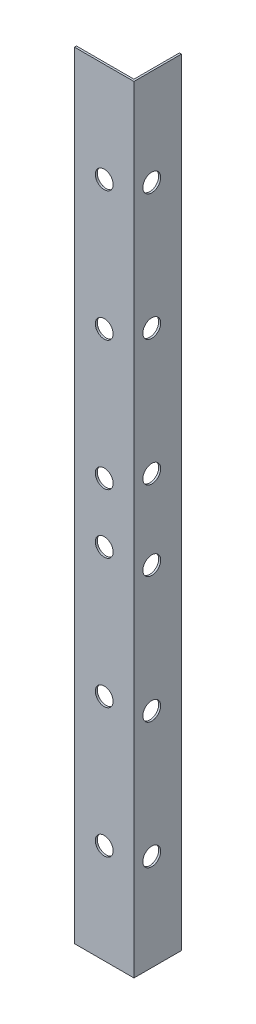
SolidWorks part; units mm, degrees
material "6061-T6 (SS)"
ref_plane "Alzado" through (0, 0, 0) normal (0, 0, 1) x (1, 0, 0)
ref_plane "Planta" through (0, 0, 0) normal (0, 1, 0) x (1, 0, 0)
ref_plane "Vista lateral" through (0, 0, 0) normal (1, 0, 0) x (0, 0, -1)
sketch "Sketch1" plane through (0, 0, 0) normal (0, 1, 0) x (1, 0, 0)
  line L0 (0, 0) -> (15, 0)
  line L1 (15, 0) -> (15, 12)
  line L2 (15, 12) -> (14.5, 12)
  line L3 (14.5, 12) -> (14.5, 0.5)
  line L4 (14.5, 0.5) -> (0, 0.5)
  line L5 (0, 0.5) -> (0, 0)
  dimension "D1" = 15
  dimension "D2" = 12
  dimension "D3" = 0.5
  dimension "D4" = 0.5
extrude "Boss-Extrude1" add sketch "Sketch1" along normal blind 196
sketch "Sketch4" plane through (0, 0, 0) normal (0, 0, 1) x (1, 0, 0)
  line L0 (15, 196) -> (15, 0) construction
  line L1 (0, 196) -> (15, 196)
  line L2 (0, 196) -> (0, 193)
  line L3 (0, 193) -> (15, 193)
  line L4 (15, 196) -> (15, 193)
  line L6 (0, 0) -> (15, 0)
  line L7 (0, 0) -> (0, 3)
  line L8 (0, 3) -> (15, 3)
  line L9 (15, 0) -> (15, 3)
  dimension "D1" = 3
  dimension "D2" = 3
extrude "Cut-Extrude3" [suppressed] cut sketch "Sketch4" against normal up to next
sketch "Sketch5" plane through (15, 0, 0) normal (1, 0, 0) x (0, 0, -1)
  circle A0 centre (4.5, 24.3333) radius 2.25
  circle A1 centre (4.5, 56.1667) radius 2.25
  circle A2 centre (4.5, 88) radius 2.25
  circle A3 centre (4.5, 108) radius 2.25
  circle A4 centre (4.5, 139.8333) radius 2.25
  circle A5 centre (4.5, 171.6667) radius 2.25
  dimension "D1" = 4.5
extrude "Cut-Extrude4" cut sketch "Sketch5" against normal up to next
sketch "Sketch6" plane through (0, 0, 0) normal (0, 0, 1) x (1, 0, 0)
  circle A0 centre (7.5, 25.1667) radius 2.25
  circle A1 centre (7.5, 57.8333) radius 2.25
  circle A2 centre (7.5, 90.5) radius 2.25
  circle A3 centre (7.5, 105.5) radius 2.25
  circle A4 centre (7.5, 138.1667) radius 2.25
  circle A5 centre (7.5, 170.8333) radius 2.25
  dimension "D1" = 4.5
extrude "Cut-Extrude5" cut sketch "Sketch6" against normal up to next
